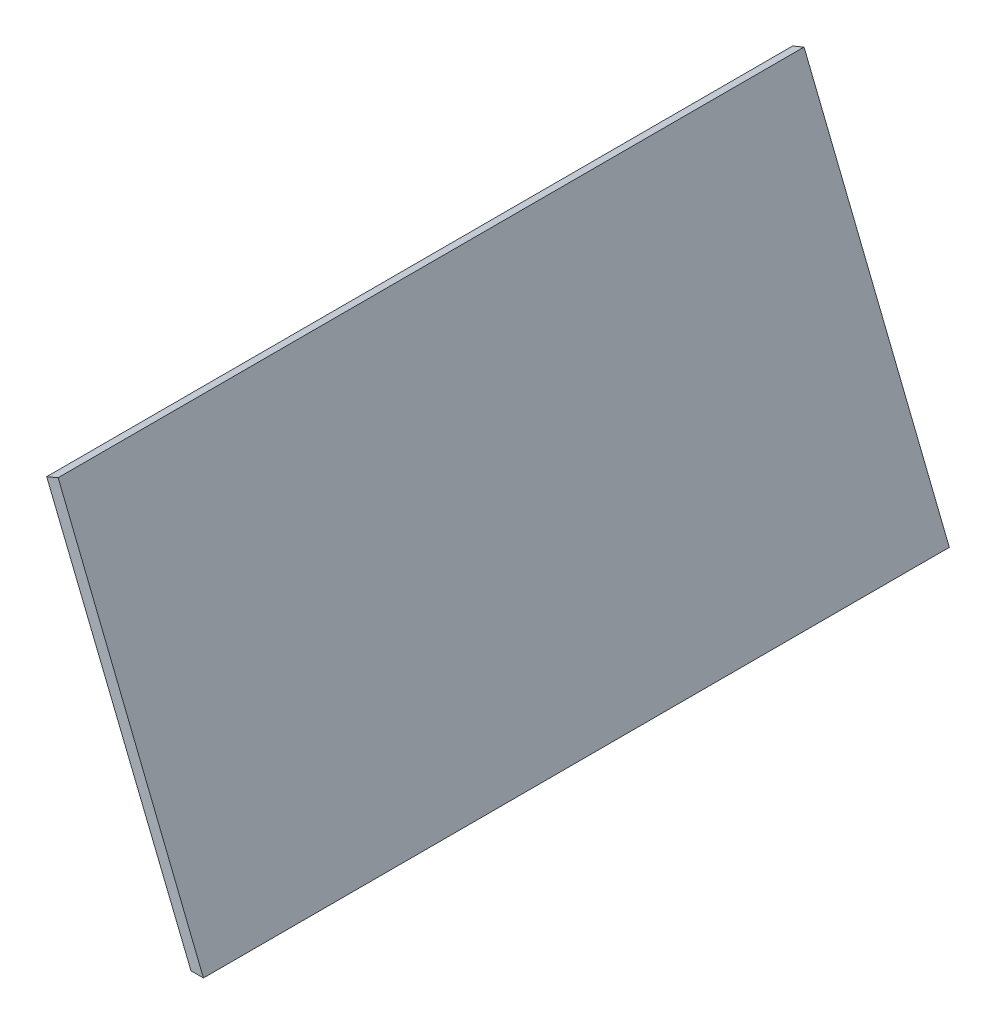
SolidWorks part; units mm, degrees
ref_plane "Plan de face" through (0, 0, 0) normal (0, 0, 1) x (1, 0, 0)
ref_plane "Plan de dessus" through (0, 0, 0) normal (0, 1, 0) x (1, 0, 0)
ref_plane "Plan de droite" through (0, 0, 0) normal (1, 0, 0) x (0, 0, -1)
sketch "Esquisse1" plane through (0, 0, 0) normal (0, 0, 1) x (1, 0, 0)
  line L0 (219.7345, 127.183) -> (103.6557, 413.4004)
  line L1 (103.6557, 413.4004) -> (112.8744, 417.2754)
  line L3 (112.8744, 417.2754) -> (229.7345, 127.183)
  line L4 (229.7345, 127.183) -> (219.7345, 127.183)
  dimension "D1" = 10
extrude "Boss.-Extru.1" add sketch "Esquisse1" along normal blind 600
